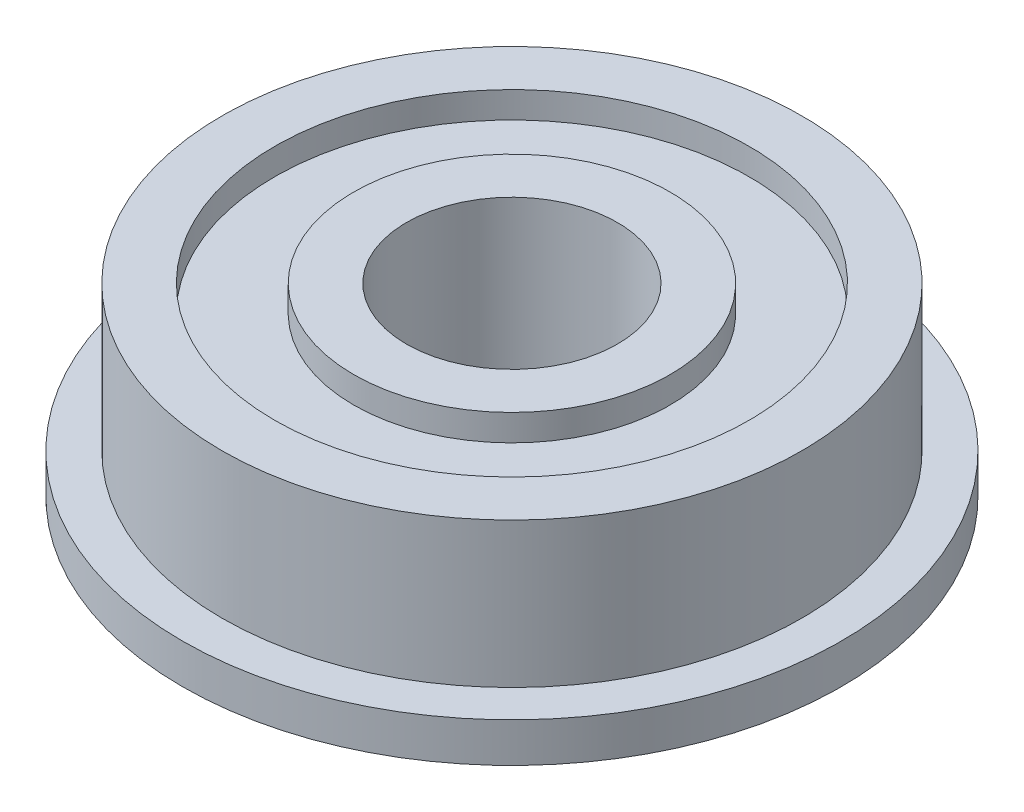
SolidWorks part; units mm, degrees
ref_plane "前基準面" through (0, 0, 0) normal (0, 0, 1) x (1, 0, 0)
ref_plane "上基準面" through (0, 0, 0) normal (0, 1, 0) x (1, 0, 0)
ref_plane "右基準面" through (0, 0, 0) normal (1, 0, 0) x (0, 0, -1)
sketch "草圖1" plane through (0, 0, 0) normal (0, 1, 0) x (1, 0, 0)
  circle A0 centre (0, 0) radius 11000
  circle A1 centre (0, 0) radius 12500
  circle A2 centre (0, 0) radius 4000
  dimension "D1" = 8000
  dimension "D2" = 22000
  dimension "D3" = 25000
extrude "填料-伸長1" add sketch "草圖1" along normal blind 7000 contours A0 A2 region at (-10688.873, 0, 0)
extrude "填料-伸長2" add sketch "草圖1<3>" along normal blind 1500 contours A1 A0 region at (-12146.4466, 0, 0)
sketch "草圖1<3>" plane through (0, 0, 0) normal (0, 1, 0) x (1, 0, 0) same geometry as "草圖1"
sketch "草圖2" plane through (0, 7000, 0) normal (0, 1, 0) x (1, 0, 0)
  circle A0 centre (0, 0) radius 6000
  circle A1 centre (0, 0) radius 9000
  dimension "D1" = 12000
  dimension "D2" = 18000
extrude "除料-伸長1" cut sketch "草圖2" against normal blind 1000
sketch "草圖3" plane through (0, 0, 0) normal (0, -1, 0) x (1, 0, 0)
  circle A0 centre (0, 0) radius 6000
  circle A1 centre (0, 0) radius 9000
extrude "除料-伸長2" cut sketch "草圖3" against normal blind 1000
